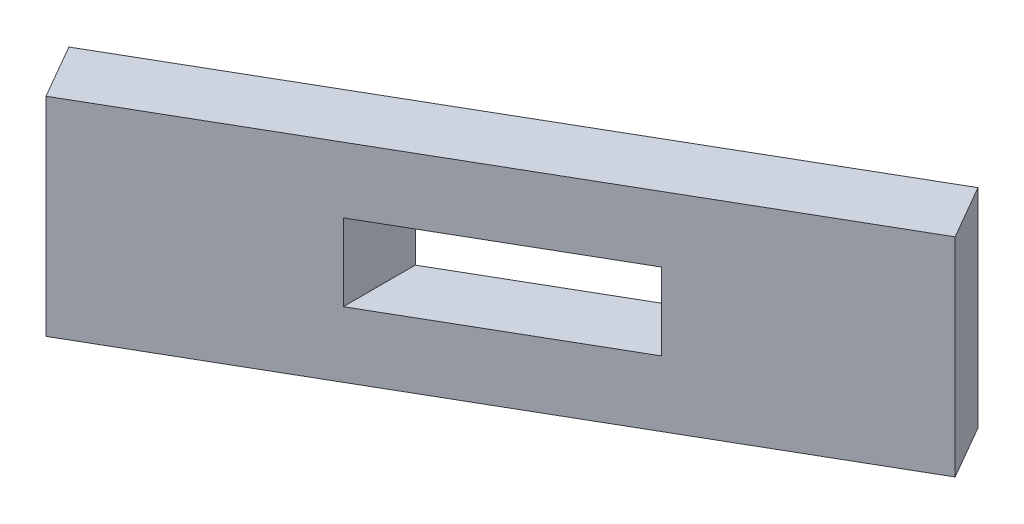
SolidWorks part; units mm, degrees
ref_plane "前基準面" through (0, 0, 0) normal (0, 0, 1) x (1, 0, 0)
ref_plane "上基準面" through (0, 0, 0) normal (0, 1, 0) x (1, 0, 0)
ref_plane "右基準面" through (0, 0, 0) normal (1, 0, 0) x (0, 0, -1)
sketch "草圖1" plane through (0, 0, 0) normal (0, 1, 0) x (1, 0, 0)
  line L0 (-24.4175, -5.9381) -> (-25.9175, -3.34)
  line L1 (-25.9175, -3.34) -> (1.7953, 12.66)
  line L2 (1.7953, 12.66) -> (3.2953, 10.0619)
  line L3 (3.2953, 10.0619) -> (-24.4175, -5.9381)
extrude "填料-伸長1" add sketch "草圖1" along normal blind 5 and the other way blind 5
sketch "草圖2" plane through (0, 0, 0) normal (0, 1, 0) x (1, 0, 0)
  line L0 (-15.3563, -0.7066) -> (-15.3563, 2.4)
  line L1 (-15.3563, -0.7066) -> (-5.6563, 4.8937)
  line L2 (-5.6563, 8.3578) -> (-5.6563, 4.8937)
  line L3 (1.7953, 12.66) -> (-25.9175, -3.34) construction
  line L4 (-24.4175, -5.9381) -> (3.2953, 10.0619) construction
  line L5 (-5.6563, 8.3578) -> (-15.3563, 2.7575)
  line L6 (-15.3563, 2.7575) -> (-15.3563, 2.4)
  dimension "D1" = 9.7
extrude "除料-伸長1" cut sketch "草圖2" against normal mid plane 3.7 contours L0 region at (-10.5063, 0, -3.8256)
